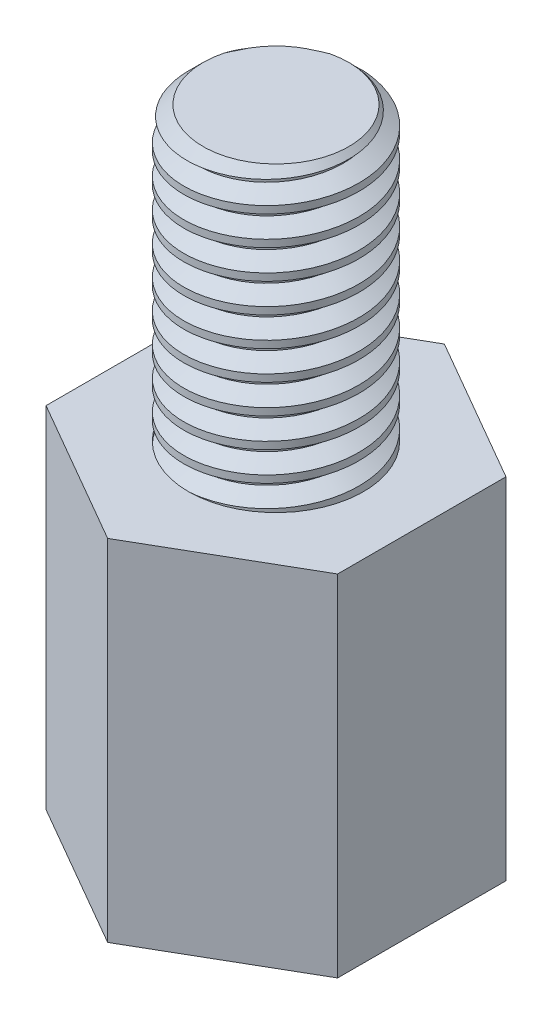
SolidWorks part; units mm, degrees
material "Tin Bearing Bronze"
ref_plane "Front Plane" through (0, 0, 0) normal (0, 0, 1) x (1, 0, 0)
ref_plane "Top Plane" through (0, 0, 0) normal (0, 1, 0) x (1, 0, 0)
ref_plane "Right Plane" through (0, 0, 0) normal (1, 0, 0) x (0, 0, -1)
sketch "Sketch2" plane through (0, 0, 0) normal (0, 1, 0) x (1, 0, 0)
  line L0 (0, 2.8868) -> (-2.5, 1.4434)
  line L1 (-2.5, 1.4434) -> (-2.5, -1.4434)
  line L2 (-2.5, -1.4434) -> (0, -2.8868)
  line L3 (0, -2.8868) -> (2.5, -1.4434)
  line L4 (2.5, -1.4434) -> (2.5, 1.4434)
  line L5 (2.5, 1.4434) -> (0, 2.8868)
  line L6 (0, -2.8868) -> (2.5, 1.4434)
  line L7 (2.5, -1.4434) -> (0, 2.8868)
  line L8 (-2.5, 1.4434) -> (2.5, 1.4434)
  line L9 (-2.5, -1.4434) -> (2.5, 1.4434) construction
  point P0 (0, 0)
  dimension "D1" = 5
extrude "Boss-Extrude1" add sketch "Sketch2" along normal blind 6 contours L9 L2 L6 L7 | L1 L9 L7 L8 | L0 L8 L7 | L7 L8 L5 | L7 L9 L8 | L9 L7 L6 | L7 L4 L6 | L3 L7 L6 region at (-0.5556, 0, -1.9245) region at (1.1111, 0, -1.9245) region at (-1.048, 0, -0.4155) region at (2.2222, 0, 0) region at (1.5278, 0, -1.2028) region at (1.8056, 0, -0.7217) region at (-0.1641, 0, 1.1153) region at (1.3889, 0, 1.4434)
sketch "Sketch3" plane through (0, 6, 0) normal (0, 1, 0) x (1, 0, 0)
  circle A0 centre (0, 0) radius 1.5
  dimension "D1" = 3
extrude "Boss-Extrude2" add sketch "Sketch3" along normal blind 5
hole_wizard "M3x0.5 Tapped Hole1" positions "Sketch8" profile "Sketch7" tap size "M3x0.5" standard "ANSI Metric"
sketch "Sketch8" plane through (0, 0, 0) normal (0, -1, 0) x (-1, 0, 0)
  point P0 (0, 0)
sketch "Sketch7" plane through (0, 0, 0) normal (1, 0, 0) x (0, 0, -1)
  line L0 (0, 0) -> (0, 6.2511)
  line L1 (0, 6.2511) -> (1.25, 5.5)
  line L2 (1.25, 5.5) -> (1.25, 0)
  line L5 (1.25, 0) -> (0, 0)
  line L10 (0, 6.2511) -> (-1.25, 5.5) construction
  line L11 (0, -6.35) -> (0, 107.95) construction
  dimension "Tap Drill Dia." = 2.5
  dimension "Tap Drill Depth" = 5.5
  dimension "Drill Angle" = 118
cosmetic thread "Hole Thread1" parameters "D1"=5.5, "D2"=3
chamfer "Chamfer1" distance 0.25 angle 45 1 edges at (0, 11, 1.5)
thread "Thread1" pitch 0.5 method cut profile "Thread Profile1" start angle 0, offset 1, length 5.5, pitch 0.5, diameter 3
ref_plane "Plane1" through (-1.5, 11.75, 0) normal (0, 0, -1) x (1, 0, 0)
sketch "Thread Profile1" plane through (-1.5, 11.75, 0) normal (0, 0, -1) x (1, 0, 0)
  line L0 (0, 0) -> (0, 0.5) construction
  line L1 (0, 0) -> (0.2706, 0.1562)
  line L2 (0.2706, 0.1562) -> (0.2706, 0.2187)
  line L3 (0.2706, 0.2187) -> (0, 0.375)
  line L4 (0.2706, 0.1875) -> (0, 0.1875) construction
  line L11 (0, 0) -> (0, 0.375)
  point P2 (0, 0)
  dimension "Pitch" = 0.5
  dimension "Profile_Angle" = 60
  dimension "Profile_Land" = 0.0625
  dimension "Profile_Height" = 0.2706
